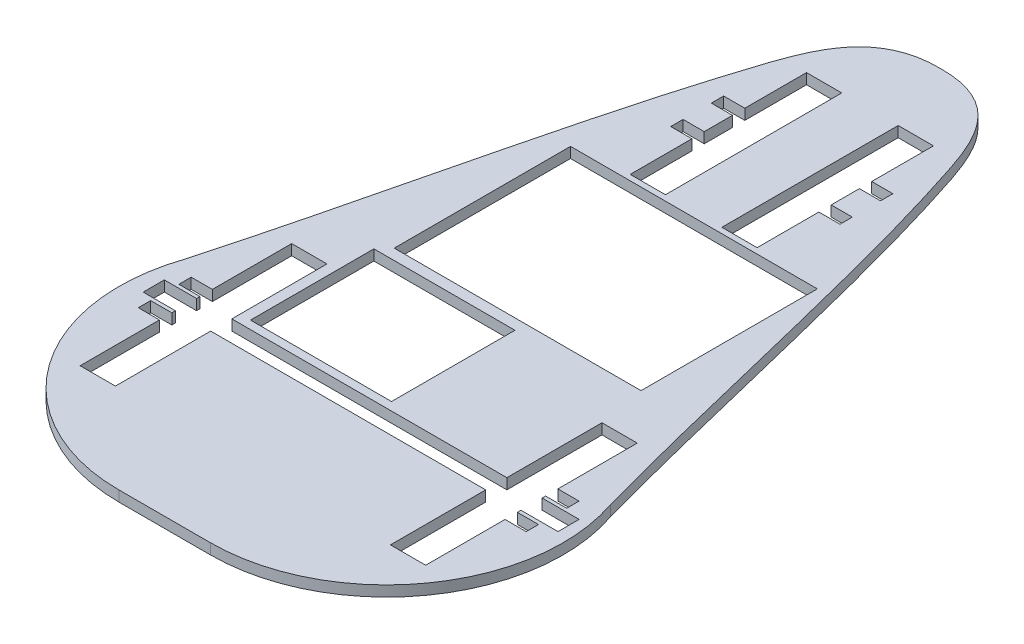
SolidWorks part; units mm, degrees
ref_plane "Front Plane" through (0, 0, 0) normal (0, 0, 1) x (1, 0, 0)
ref_plane "Top Plane" through (0, 0, 0) normal (0, 1, 0) x (1, 0, 0)
ref_plane "Right Plane" through (0, 0, 0) normal (1, 0, 0) x (0, 0, -1)
sketch "Sketch1" plane through (0, 0, 0) normal (0, 1, 0) x (1, 0, 0)
  line L0 (54.9211, 210.7172) -> (54.9211, -9.2828) construction
  line L1 (41.947, -9.2828) -> (67.8952, -9.2828)
  line L5 (-0.0789, 53.2172) -> (5.9211, 53.2172)
  line L6 (5.9211, 75.7172) -> (15.9211, 75.7172)
  line L7 (54.9211, -9.2828) -> (64.9211, -9.2828)
  line L8 (54.9211, -9.2828) -> (44.9211, -9.2828)
  line L9 (5.9211, 75.7172) -> (5.9211, 15.7172)
  line L10 (5.9211, 15.7172) -> (15.9211, 15.7172)
  line L11 (15.9211, 75.7172) -> (15.9211, 15.7172)
  line L12 (5.9211, 75.7172) -> (15.9211, 15.7172) construction
  line L13 (5.9211, 15.7172) -> (15.9211, 75.7172) construction
  line L18 (-0.0789, 49.7172) -> (5.9211, 41.7172) construction
  line L19 (-0.0789, 41.7172) -> (5.9211, 49.7172) construction
  line L20 (-0.0789, 53.2172) -> (-0.0789, 49.7172)
  line L21 (-0.0789, 49.7172) -> (5.9211, 49.7172)
  line L22 (5.9211, 53.2172) -> (5.9211, 49.7172)
  line L23 (-0.0789, 41.7172) -> (5.9211, 41.7172)
  line L24 (-0.0789, 41.7172) -> (-0.0789, 38.2172)
  line L25 (-0.0789, 38.2172) -> (5.9211, 38.2172)
  line L26 (5.9211, 41.7172) -> (5.9211, 38.2172)
  line L27 (109.9211, 41.7172) -> (109.9211, 38.2172)
  line L28 (109.9211, 38.2172) -> (103.9211, 38.2172)
  line L29 (103.9211, 41.7172) -> (103.9211, 38.2172)
  line L30 (109.9211, 41.7172) -> (103.9211, 41.7172)
  line L31 (109.9211, 53.2172) -> (109.9211, 49.7172)
  line L32 (109.9211, 49.7172) -> (103.9211, 49.7172)
  line L33 (103.9211, 53.2172) -> (103.9211, 49.7172)
  line L34 (109.9211, 53.2172) -> (103.9211, 53.2172)
  line L35 (103.9211, 15.7172) -> (93.9211, 15.7172)
  line L36 (93.9211, 75.7172) -> (93.9211, 15.7172)
  line L37 (103.9211, 75.7172) -> (93.9211, 75.7172)
  line L38 (103.9211, 75.7172) -> (103.9211, 15.7172)
  line L39 (30.9211, 173.2172) -> (36.9211, 173.2172)
  line L40 (36.9211, 190.7172) -> (46.9211, 190.7172)
  line L41 (36.9211, 190.7172) -> (36.9211, 140.7172)
  line L42 (36.9211, 140.7172) -> (46.9211, 140.7172)
  line L43 (46.9211, 190.7172) -> (46.9211, 140.7172)
  line L44 (36.9211, 190.7172) -> (46.9211, 140.7172) construction
  line L45 (36.9211, 140.7172) -> (46.9211, 190.7172) construction
  line L47 (21.5766, 139.1342) -> (91.5766, 139.1342)
  line L48 (30.9211, 173.2172) -> (30.9211, 169.7172)
  line L49 (30.9211, 169.7172) -> (36.9211, 169.7172)
  line L50 (36.9211, 173.2172) -> (36.9211, 169.7172)
  line L51 (30.9211, 161.7172) -> (36.9211, 161.7172)
  line L52 (30.9211, 161.7172) -> (30.9211, 158.2172)
  line L53 (30.9211, 158.2172) -> (36.9211, 158.2172)
  line L54 (36.9211, 161.7172) -> (36.9211, 158.2172)
  line L55 (78.9211, 161.7172) -> (78.9211, 158.2172)
  line L56 (78.9211, 158.2172) -> (72.9211, 158.2172)
  line L57 (72.9211, 161.7172) -> (72.9211, 158.2172)
  line L58 (78.9211, 161.7172) -> (72.9211, 161.7172)
  line L59 (78.9211, 173.2172) -> (78.9211, 169.7172)
  line L60 (78.9211, 169.7172) -> (72.9211, 169.7172)
  line L61 (72.9211, 173.2172) -> (72.9211, 169.7172)
  line L62 (78.9211, 173.2172) -> (72.9211, 173.2172)
  line L63 (72.9211, 140.7172) -> (62.9211, 140.7172)
  line L64 (62.9211, 190.7172) -> (62.9211, 140.7172)
  line L65 (72.9211, 190.7172) -> (62.9211, 190.7172)
  line L66 (72.9211, 190.7172) -> (72.9211, 140.7172)
  line L67 (21.5766, 139.1342) -> (21.5766, 89.1342)
  line L68 (21.5766, 89.1342) -> (91.5766, 89.1342)
  line L69 (91.5766, 139.1342) -> (91.5766, 89.1342)
  line L70 (18.8707, 86.0824) -> (58.8707, 86.0824)
  line L71 (18.8707, 86.0824) -> (18.8707, 51.0824)
  line L72 (18.8707, 51.0824) -> (58.8707, 51.0824)
  line L73 (58.8707, 86.0824) -> (58.8707, 51.0824)
  line L74 (-3.2215, 48.7364) -> (114.4207, 48.7364)
  line L75 (-3.2215, 48.7364) -> (-3.2215, 42.7364)
  line L76 (-3.2215, 42.7364) -> (114.4207, 42.7364)
  line L77 (114.4207, 48.7364) -> (114.4207, 42.7364)
  arc A0 (41.947, -9.2828) -> (-5.4028, 56.7793) centre (41.947, 40.7172) cw
  arc A1 (67.8952, -9.2828) -> (115.245, 56.7793) centre (67.8952, 40.7172) ccw
  spline S0 degree 3 poles (54.9211, 210.7172) (54.0308, 210.7172) (36.7248, 210.3077) (26.6736, 181.7821) (12.5146, 130.3071) (2.5819, 85.5886) (-5.4028, 56.7793) knots 0 0 0 0 0.011068 0.221366 0.459883 1 1 1 1
  spline S1 degree 3 poles (54.9211, 210.7172) (55.8114, 210.7172) (73.1174, 210.3077) (83.1686, 181.7821) (97.3276, 130.3071) (107.2603, 85.5886) (115.245, 56.7793) knots 0 0 0 0 0.011068 0.221366 0.459883 1 1 1 1
  point P4 (2.9211, 45.7172)
  point P21 (120, 0)
  point P24 (10.9211, 45.7172)
  point P50 (41.9211, 165.7172)
  dimension "D6" = 10
  dimension "D7" = 50
  dimension "D10" = 8
  dimension "D2" = 173.1277
  dimension "D1" = 220
  dimension "D3" = 60.3239
  dimension "D4" = 10
  dimension "D5" = 10
  dimension "D8" = 60
  dimension "D9" = 6
  dimension "D11" = 25
  dimension "D12" = 8
  dimension "D13" = 0
  dimension "D14" = 22.5
  dimension "D15" = 3.5
  dimension "D16" = 0
  dimension "D17" = 22.5
  dimension "D18" = 39
  dimension "D19" = 6
  dimension "D20" = 10
  dimension "D21" = 50
  dimension "D22" = 20
  dimension "D23" = 8
  dimension "D24" = 3.5
  dimension "D25" = 17.5
  dimension "D26" = 8
  dimension "D27" = 0
  dimension "D28" = 6
  dimension "D29" = 70
  dimension "D30" = 50
  dimension "D31" = 35
  dimension "D32" = 40
  dimension "D33" = 6
extrude "Boss-Extrude1" add sketch "Sketch1" along normal blind 3 contours L0 S0 A0 L1 | S1 L0 L1 A1 region at (3.3681, 0, -13.0659)
